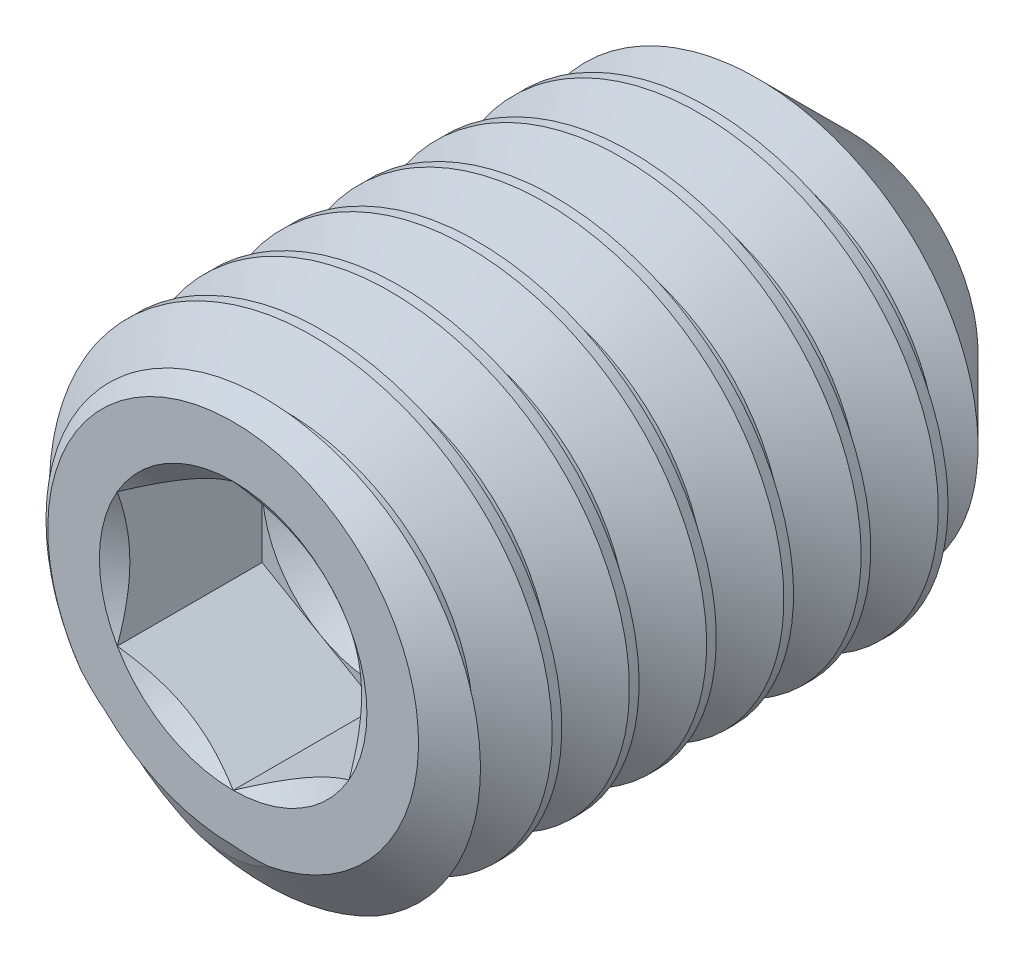
SolidWorks part; units mm, degrees
ref_plane "Front" through (0, 0, 0) normal (0, 0, 1) x (1, 0, 0)
ref_plane "Top" through (0, 0, 0) normal (0, 1, 0) x (1, 0, 0)
ref_plane "Right" through (0, 0, 0) normal (1, 0, 0) x (0, 0, -1)
sketch "Body Sketch" plane through (0, 0, 0) normal (1, 0, 0) x (0, 0, -1)
  line L0 (-1.7531, 0) -> (-1.7531, 1.2)
  line L1 (-1.7531, 1.2) -> (-1.543, 1.5)
  line L2 (-1.543, 1.5) -> (1.5689, 1.5)
  line L3 (1.5689, 1.5) -> (2.2469, 0.8219)
  line L4 (0.0129, 1.5) -> (0.0129, -1.5) construction
  line L5 (1.7531, 0) -> (-1.7531, 0)
  line L6 (-1.7531, 1.2) -> (-1.7531, -1.2) construction
  line L7 (1.7531, 0) -> (2.2469, 0.8219)
  line L8 (1.7531, 0) -> (2.2469, -0.8219) construction
  line L10 (1.7531, 0) -> (2.2469, 0) construction
  line L11 (2.2469, 0.8219) -> (2.2469, 0) construction
  point P11 (0.0129, 0)
  dimension "Top Chamfer" = 35
  dimension "Diameter" = 3
  dimension "D1" = 2.4
  dimension "D2" = 118
  dimension "D3" = 45
revolve "Body Revolve" add sketch "Body Sketch" angle 360 about L5
ref_plane "Bottom of Tip Plane" through (0, 0, -2.2469) normal (0, 0, 1) x (1, 0, 0)
sketch "Spiral Sketch" plane through (0, 0, -2.2469) normal (0, 0, 1) x (1, 0, 0)
  circle A0 centre (0, 0) radius 1.5 construction
  circle A1 centre (0, 0) radius 1.5
curve "Helix/Spiral" pitch 0.5 height 5.5 radius 1.5 centre (0, 0, -2.2469) axis (0, 0, 1) start towards (0, 1, 0) parameters "Thread Pitch"=0.5
sketch "Cut Sweep Sketch" plane through (0, 0, 0) normal (1, 0, 0) x (0, 0, -1)
  line L0 (2.2469, 1.5) -> (2.6844, 1.5)
  line L1 (2.6844, 1.5) -> (2.4969, 1.1752)
  line L2 (2.4969, 1.1752) -> (2.4344, 1.1752)
  line L3 (2.4344, 1.1752) -> (2.2469, 1.5)
  line L4 (2.3407, 1.3376) -> (2.5907, 1.3376) construction
  line L6 (-1.543, 1.5) -> (1.5689, 1.5) construction
  dimension "D1" = 0.0625
  dimension "D3" = 60
  dimension "D2" = 0.25
sweep "Cut Sweep" cut profiles "Cut Sweep Sketch" path "Helix/Spiral" align with end faces yes
sketch "Hex Sketch" plane through (0, 0, 1.7531) normal (0, 0, 1) x (1, 0, 0)
  line L1 (0, 0.866) -> (-0.75, 0.433)
  line L2 (-0.75, 0.433) -> (-0.75, -0.433)
  line L3 (-0.75, -0.433) -> (0, -0.866)
  line L4 (0, -0.866) -> (0.75, -0.433)
  line L5 (0.75, -0.433) -> (0.75, 0.433)
  line L6 (0.75, 0.433) -> (0, 0.866)
  circle A0 centre (0, 0) radius 0.75 construction
  dimension "Hex" = 1.5
extrude "Hex Extrude" cut sketch "Hex Sketch" against normal blind 0.9375
sketch "Hex Entry Sketch" plane through (0, 0, 1.7531) normal (0, 0, 1) x (1, 0, 0)
  circle A0 centre (0, 0) radius 0.866
extrude "Hex Entry Extrude" cut sketch "Hex Entry Sketch" against normal through all draft 55
sketch "Hex Bottom Sketch" plane through (0, 0, 0.8156) normal (0, 0, 1) x (1, 0, 0)
  circle A0 centre (0, 0) radius 0.75 construction
  circle A1 centre (0, 0) radius 0.75
extrude "Hex Bottom Extrude" cut sketch "Hex Bottom Sketch" against normal through all draft 60
ref_axis "Centerline Axis" through (0, 0, -1.7531) along (0, 0, 1)
equation "\"D1@Cut Sweep Sketch\" = \"Thread Pitch@Helix/Spiral\" * .125"
equation "\"D2@Cut Sweep Sketch\" = \"Thread Pitch@Helix/Spiral\" * .5"
equation "\"D3@Helix/Spiral\" = \"Length@Body Sketch\" + \"Thread Pitch@Helix/Spiral\""
equation "\"hex Depth@Hex Extrude\" = \"Hex@Hex Sketch\" * .625"
equation "\"D1@Body Sketch\" = \"Diameter@Body Sketch\" * .8"
equation "\"Diameter\"= 3mm"
equation "\"Thread Pitch\"= 0.5mm"
equation "\"Hex Size\"= 1.5mm"
equation "\"Diameter@Body Sketch\"=\"Diameter\""
equation "\"Thread Pitch@Helix/Spiral\"=\"Thread Pitch\""
equation "\"Hex@Hex Sketch\"=\"Hex Size\""
